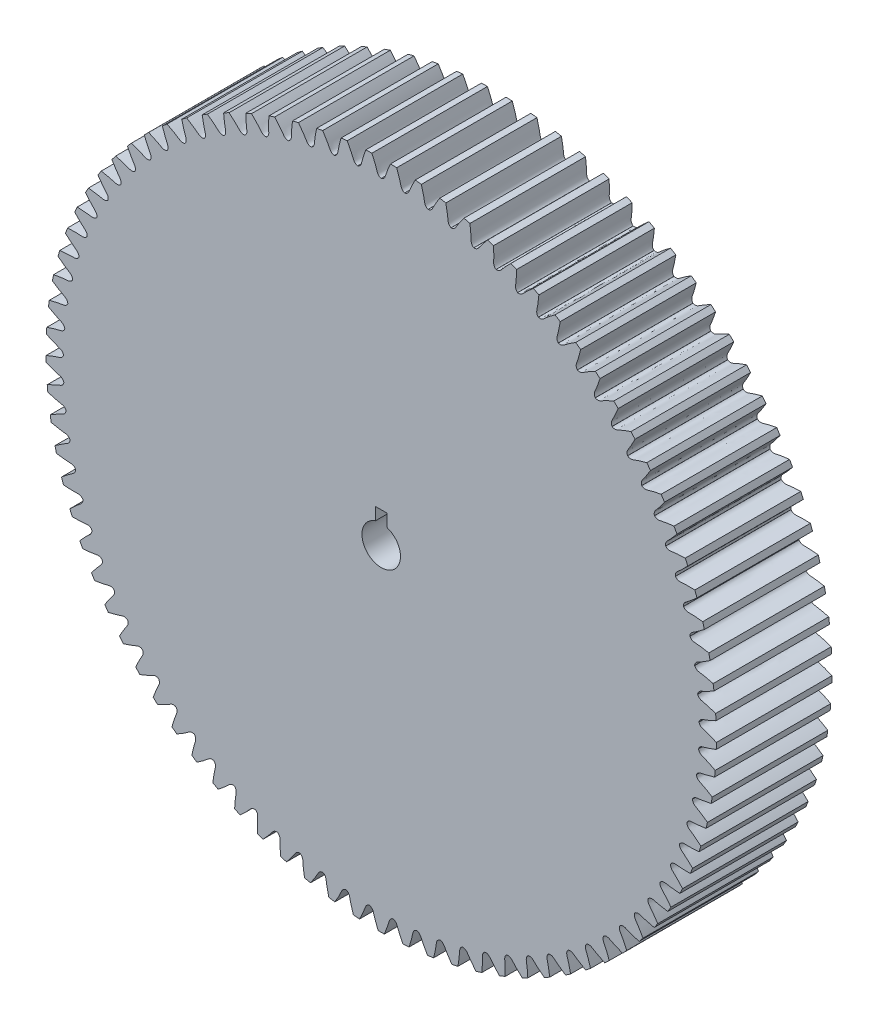
SolidWorks part; units mm, degrees
ref_plane "前视基准面" through (0, 0, 0) normal (0, 0, 1) x (1, 0, 0)
ref_plane "上视基准面" through (0, 0, 0) normal (0, 1, 0) x (1, 0, 0)
ref_plane "右视基准面" through (0, 0, 0) normal (1, 0, 0) x (0, 0, -1)
other "Configuration Table"
sketch "草图1" plane through (0, 0, 0) normal (0, 0, 1) x (1, 0, 0)
  circle A0 centre (0, 0) radius 87
extrude "凸台-拉伸1" add sketch "草图1" along normal blind 30
ref_axis "基准轴1" through (0, 0, -1.5) along (0, 0, 1)
sketch "草图2" plane through (0, 0, 0) normal (0, 0, 1) x (1, 0, 0)
  line L0 (0, 0) -> (0, 87) construction
  circle A0 centre (0, 0) radius 87 construction
  arc A1 (0.01, 82.4987) -> (-0.01, 82.4987) centre (0, 0) ccw
  arc A2 (10.8119, 99.0711) -> (-10.8119, 99.0711) centre (0, 0) ccw
  spline S0 degree 3 poles (0.01, 82.4987) (0.8672, 82.7223) (1.0468, 83.5602) (1.3964, 84.523) (1.5957, 85.0562) (1.819, 85.6141) (2.0654, 86.1971) (2.3365, 86.8042) (2.6333, 87.4347) (2.9568, 88.0877) (3.308, 88.7624) (3.688, 89.4581) (4.0977, 90.1737) (4.5381, 90.9084) (5.01, 91.6613) (5.5144, 92.4313) (6.0521, 93.2174) (6.624, 94.0186) (7.2309, 94.8338) (7.8735, 95.662) (8.5526, 96.502) (9.5216, 97.6526) (10.2849, 98.5051) (10.8119, 99.0711) knots 0 0 0 0 0.098795 0.125702 0.15421 0.184318 0.216027 0.249337 0.284248 0.320759 0.358872 0.398585 0.439898 0.482813 0.527328 0.573444 0.621161 0.670479 0.721397 0.773916 0.828036 0.883756 1 1 1 1
  spline S1 degree 3 poles (-0.01, 82.4987) (-0.8672, 82.7223) (-1.0468, 83.5602) (-1.3964, 84.523) (-1.5957, 85.0562) (-1.819, 85.6141) (-2.0654, 86.1971) (-2.3365, 86.8042) (-2.6333, 87.4347) (-2.9568, 88.0877) (-3.308, 88.7624) (-3.688, 89.4581) (-4.0977, 90.1737) (-4.5381, 90.9084) (-5.01, 91.6613) (-5.5144, 92.4313) (-6.0521, 93.2174) (-6.624, 94.0186) (-7.2309, 94.8338) (-7.8735, 95.662) (-8.5526, 96.502) (-9.5216, 97.6526) (-10.2849, 98.5051) (-10.8119, 99.0711) knots 0 0 0 0 0.098795 0.125702 0.15421 0.184318 0.216027 0.249337 0.284248 0.320759 0.358872 0.398585 0.439898 0.482813 0.527328 0.573444 0.621161 0.670479 0.721397 0.773916 0.828036 0.883756 1 1 1 1
extrude "切除-拉伸1" cut sketch "草图2" along normal through all
pattern_circular "阵列(圆周)1" count 85 every 4.235 about axis through (0, 0, -1.5) along (0, 0, 1) of "切除-拉伸1"
sketch "草图3" plane through (0, 0, 0) normal (0, 0, 1) x (1, 0, 0)
  circle A0 centre (0, 0) radius 85 construction
  dimension "Dn" = 170
sketch "草图4" plane through (0, 0, 30) normal (0, 0, 1) x (1, 0, 0)
  line L0 (0, 0) -> (-1.5, 0)
  line L1 (-1.5, 0) -> (-1.5, 8)
  line L2 (-1.5, 8) -> (1.5, 8)
  line L3 (1.5, 8) -> (1.5, 0)
  line L4 (1.5, 0) -> (0, 0)
  circle A0 centre (0, 0) radius 5
extrude "切除-拉伸2" cut sketch "草图4" against normal through all contours A0 L3 L2 L1 | L3 A0 L1 L0 L4 | L1 A0 L3 L4 L0 region at (0, -0.5704, 30) region at (0, 2.4625, 30) region at (0, 6.4612, 30)
